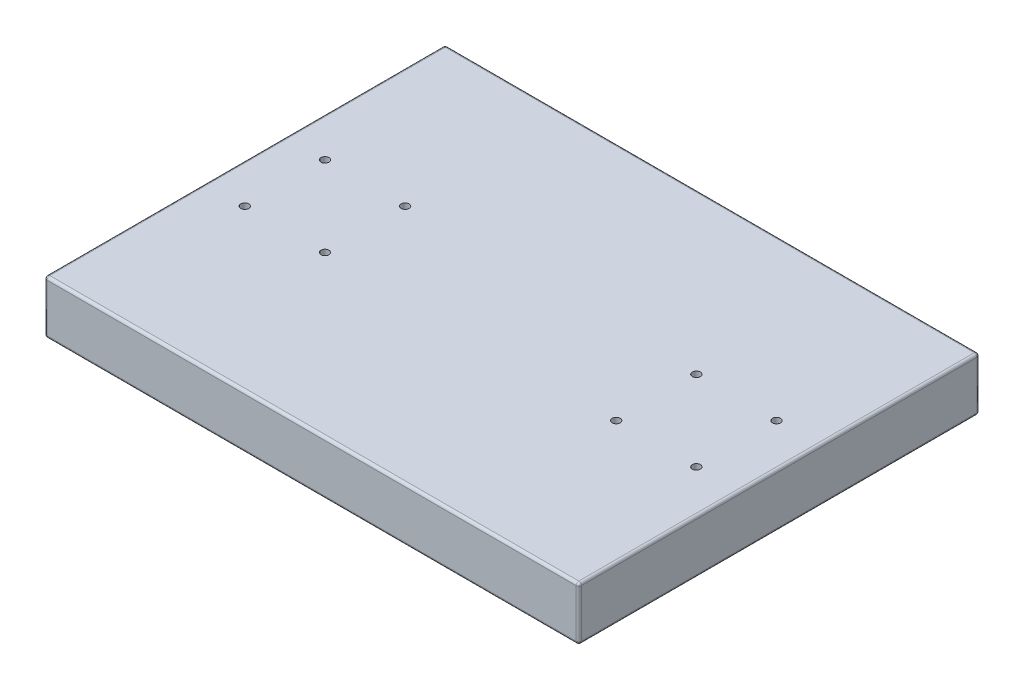
SolidWorks part; units mm, degrees
ref_plane "Front Plane" through (0, 0, 0) normal (0, 0, 1) x (1, 0, 0)
ref_plane "Top Plane" through (0, 0, 0) normal (0, 1, 0) x (1, 0, 0)
ref_plane "Right Plane" through (0, 0, 0) normal (1, 0, 0) x (0, 0, -1)
sketch "Sketch2" plane through (0, 0, 0) normal (0, 1, 0) x (1, 0, 0)
  line L0 (-136.9403, 0) -> (182.8358, 0) construction
  line L1 (0, 108.0224) -> (0, -102.4254) construction
  line L3 (-100, -75) -> (100, -75)
  line L4 (-100, -75) -> (-100, 75)
  line L5 (-100, 75) -> (100, 75)
  line L6 (100, -75) -> (100, 75)
  line L7 (-100, -75) -> (100, 75) construction
  line L8 (-100, 75) -> (100, -75) construction
  point P5 (0, 0)
  dimension "D1" = 200
  dimension "D2" = 150
extrude "Boss-Extrude1" add sketch "Sketch2" along normal blind 20
fillet "Fillet1" radius 1 11 edges at (100, 10, 75) (100, 20, 0) (100, 10, -75) (100, 0, 0) (-100, 0, 0) (-100, 10, -75) (0, 0, -75) (0, 0, 75) (0, 20, 75) (0, 20, -75) (-100, 20, 0)
fillet "Fillet2" radius 1 3 edges at (-99.7071, 19.7071, 74.7071) (-99.7071, 0.2929, 74.7071) (-100, 10, 75)
sketch "Sketch3" plane through (0, 20, 0) normal (0, 1, 0) x (1, 0, 0)
  line L0 (111.8275, 0) -> (-115.2777, 0) construction
  line L1 (111.8275, 15) -> (-20.7013, 15) construction
  line L2 (111.8275, -15) -> (-18.8747, -15) construction
  line L4 (69, 43.9395) -> (69, -39.2716) construction
  line L5 (99, -74) -> (99, 74) construction
  circle A0 centre (84, 15) radius 1.5
  circle A1 centre (54, 15) radius 1.5
  circle A2 centre (54, -15) radius 1.5
  circle A3 centre (84, -15) radius 1.5
  dimension "D4" = 3
  dimension "D5" = 3
  dimension "D6" = 3
  dimension "D7" = 3
  dimension "D10" = 15
  dimension "D1" = 15
  dimension "D2" = 15
  dimension "D3" = 30
  dimension "D8" = 15
  dimension "D9" = 15
  dimension "D11" = 15
extrude "Cut-Extrude1" cut sketch "Sketch3" against normal blind 20
sketch "Sketch4" plane through (0, 20, 0) normal (0, 1, 0) x (1, 0, 0)
  line L0 (84, -15) -> (-90.5174, -15) construction
  line L1 (84, 15) -> (-90.5174, 15) construction
  line L2 (91.7351, 0) -> (-97.0119, 0) construction
  line L3 (-100, 22.2082) -> (-100, -21.6167) construction
  line L4 (-100, -74) -> (-100, 74) construction
  circle A0 centre (-85, 15) radius 1.5
  circle A1 centre (-55, 15) radius 1.5
  circle A2 centre (-85, -15) radius 1.5
  circle A3 centre (-55, -15) radius 1.5
  point P21 (0, 0)
  point P22 (0, 0)
  dimension "D3" = 3
  dimension "D4" = 3
  dimension "D5" = 3
  dimension "D6" = 3
  dimension "D1" = 15
  dimension "D2" = 15
  dimension "D7" = 30
  dimension "D8" = 30
extrude "Cut-Extrude2" cut sketch "Sketch4" against normal blind 20
